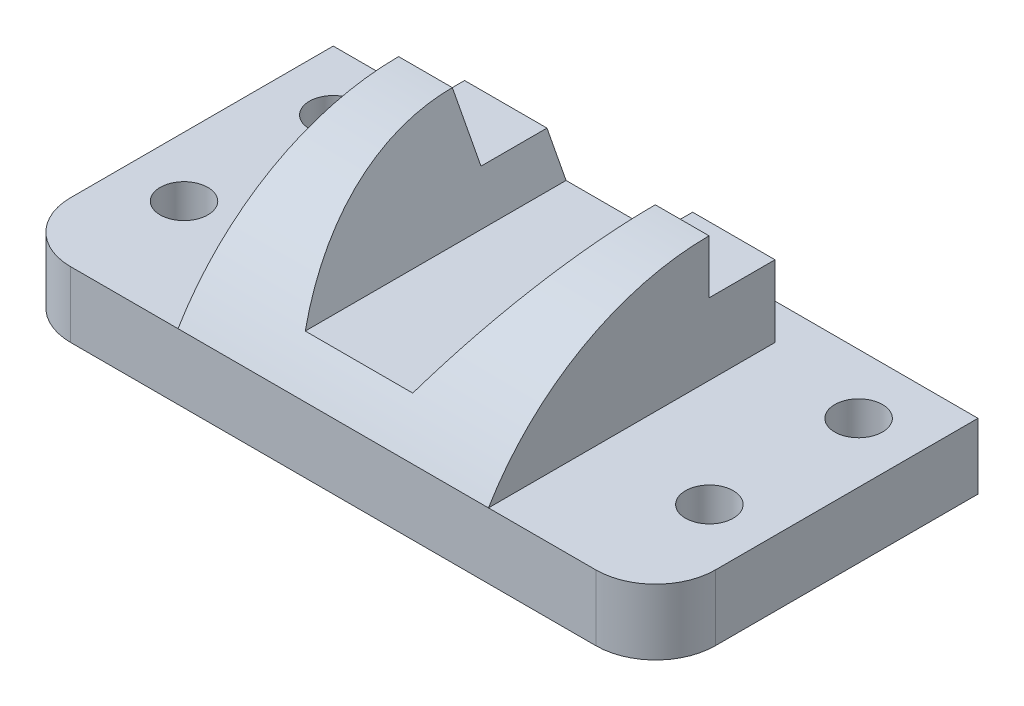
SolidWorks part; units mm, degrees
ref_plane "Front Plane" through (0, 0, 0) normal (0, 0, 1) x (1, 0, 0)
ref_plane "Top Plane" through (0, 0, 0) normal (0, 1, 0) x (1, 0, 0)
ref_plane "Right Plane" through (0, 0, 0) normal (1, 0, 0) x (0, 0, -1)
sketch "Sketch1" plane through (0, 0, 0) normal (0, 1, 0) x (1, 0, 0)
  line L0 (0, -1.7157) -> (0, 4.9666) construction
  line L1 (54, -27) -> (-54, -27)
  line L2 (54, -27) -> (54, 27)
  line L3 (54, 27) -> (-54, 27)
  line L4 (-54, -27) -> (-54, 27)
  line L5 (54, -27) -> (-54, 27) construction
  line L6 (54, 27) -> (-54, -27) construction
  circle A2 centre (-44, -8) radius 4
  circle A3 centre (-44, 17) radius 4
  circle A4 centre (44, 17) radius 4
  circle A5 centre (44, -8) radius 4
  point P0 (0, 0)
  point P12 (0, 0)
  dimension "D8" = 8
  dimension "D9" = 8
  dimension "D1" = 54
  dimension "D2" = 108
  dimension "D5" = 10
  dimension "D6" = 10
  dimension "D7" = 25
extrude "Boss-Extrude3" add sketch "Sketch1" along normal blind 11
sketch "Sketch4" plane through (0, 0, 0) normal (1, 0, 0) x (0, 0, -1)
  line L0 (-27, 11) -> (27, 11) construction
  line L1 (9.9459, 32) -> (9.9459, 23)
  line L2 (9.9459, 23) -> (21, 23)
  line L3 (21, 23) -> (21, 11)
  line L4 (27, 11) -> (27, 0) construction
  line L5 (21, 11) -> (-27, 11)
  arc A0 (-27, 11) -> (9.9459, 32) centre (9.9459, -11) cw
  dimension "D4" = 43
  dimension "D1" = 6
  dimension "D2" = 12
  dimension "D3" = 21
extrude "Boss-Extrude4" add sketch "Sketch4" along normal mid plane 52
sketch "Sketch5" plane through (0, 0, 0) normal (0, 0, 1) x (1, 0, 0)
  line L0 (-9, 17) -> (9, 17)
  line L1 (9, 17) -> (17, 32)
  line L2 (26, 32) -> (-26, 32) construction
  line L3 (-9, 17) -> (-17, 32)
  line L4 (0, -1.7642) -> (0, 4.7586) construction
  line L5 (26, 11) -> (-26, 11) construction
  line L6 (17, 32) -> (26, 32)
  line L7 (26, 32) -> (26, 11)
  line L8 (26, 11) -> (-26, 11)
  line L9 (-26, 11) -> (-26, 32)
  line L10 (-26, 32) -> (-17, 32)
  line L11 (17, 32) -> (-17, 32)
  circle A0 centre (0, 32) radius 15 construction
  dimension "D3" = 30
  dimension "D1" = 18
  dimension "D2" = 6
extrude "Cut-Extrude1" cut sketch "Sketch5" against normal up to next and the other way up to next contours L1 L11 L3 L0 region at (0, 25.2692, 0)
fillet "Fillet1" radius 10 2 edges at (-54, 5.5, 27) (54, 5.5, 27)
